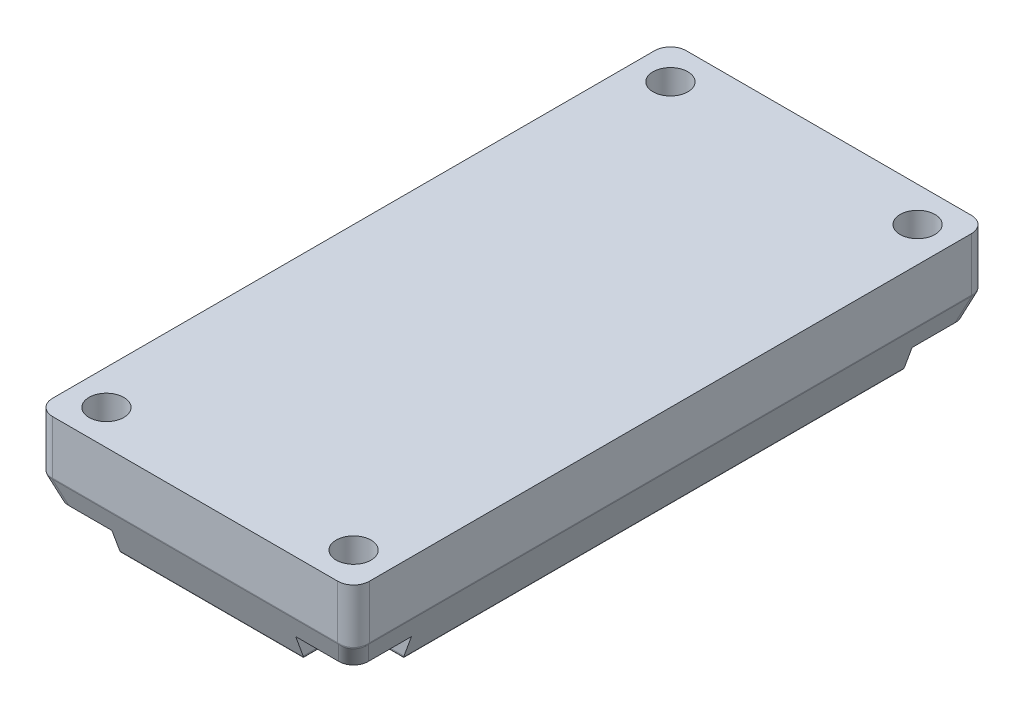
SolidWorks part; units mm, degrees
material "Polyethylene Cross-Linked"
ref_plane "Front Plane" through (0, 0, 0) normal (0, 0, 1) x (1, 0, 0)
ref_plane "Top Plane" through (0, 0, 0) normal (0, 1, 0) x (1, 0, 0)
ref_plane "Right Plane" through (0, 0, 0) normal (1, 0, 0) x (0, 0, -1)
sketch "Sketch1" plane through (0, 0, 0) normal (0, 1, 0) x (1, 0, 0)
  line L1 (-10, 20) -> (10, 20)
  line L2 (-10, 20) -> (-10, -20)
  line L3 (-10, -20) -> (10, -20)
  line L4 (10, 20) -> (10, -20)
  line L5 (-10, 20) -> (10, -20) construction
  line L6 (-10, -20) -> (10, 20) construction
  point P0 (0, 0)
  dimension "D1" = 20
  dimension "D2" = 40
extrude "Boss-Extrude1" add sketch "Sketch1" against normal blind 6.4
sketch "Sketch2" plane through (0, -6.4, 0) normal (0, -1, 0) x (-1, 0, 0)
  line L0 (5.8, -17.6) -> (5.8, -20)
  line L1 (10, -20) -> (-10, -20) construction
  line L2 (7.6, -15.8) -> (10, -15.8)
  line L3 (10, 20) -> (10, -20) construction
  line L4 (5.8, -20) -> (10, -20)
  line L5 (10, -20) -> (10, -15.8)
  arc A0 (7.6, -15.8) -> (5.8, -17.6) centre (7.6, -17.6) ccw
  dimension "D3" = 3.6
  dimension "D1" = 4.2
  dimension "D2" = 4.2
extrude "Cut-Extrude1" cut sketch "Sketch2" against normal blind 1.5
hole_wizard "M2 Clearance Hole1" positions "Sketch8" profile "Sketch7" hole size "M2" standard "ANSI Metric" end condition through all
sketch "Sketch8" plane through (0, -4.9, 0) normal (0, -1, 0) x (-1, 0, 0)
  line L0 (10, -20) -> (10, -15.8) construction
  line L1 (5.8, -20) -> (10, -20) construction
  point P0 (7.8, -17.8)
  dimension "D1" = 2.2
  dimension "D2" = 2.2
sketch "Sketch7" plane through (-7.8, -4.9, 17.8) normal (1, 0, 0) x (0, 0, -1)
  line L0 (0, 0) -> (0, 4.9)
  line L1 (0, 4.9) -> (1.1, 4.9)
  line L2 (1.1, 4.9) -> (1.1, 0)
  line L5 (1.1, 0) -> (0, 0)
  line L11 (0, -6.35) -> (0, 107.95) construction
  dimension "Thru Hole Dia." = 2.2
  dimension "Thru Hole Depth" = 4.9
mirror "Mirror1" about plane through (0, 0, 0) normal (1, 0, 0) of "M2 Clearance Hole1", "Cut-Extrude1"
mirror "Mirror2" about plane through (0, 0, 0) normal (0, 0, 1) of "Mirror1", "Cut-Extrude1"
sketch "Sketch3" plane through (0, 0, 0) normal (0, 0, 1) x (1, 0, 0)
  line L0 (10, -3.4) -> (10, -6.4)
  line L1 (10, -4.9) -> (10, 0) construction
  line L2 (10, -6.4) -> (8.9081, -6.4)
  line L3 (10, -6.4) -> (7.6, -6.4) construction
  line L4 (8.9081, -6.4) -> (10, -3.4)
  dimension "D1" = 3
  dimension "D2" = 20
extrude "Cut-Extrude2" cut sketch "Sketch3" against normal through all both and the other way through all
mirror "Mirror3" about plane through (0, 0, 0) normal (1, 0, 0) of "Cut-Extrude2"
sketch "Sketch4" plane through (0, 0, 0) normal (1, 0, 0) x (0, 0, -1)
  line L0 (20, -3.4) -> (18.9081, -6.4)
  line L1 (20, -3.4) -> (20, 0) construction
  line L2 (17.6, -6.4) -> (20, -6.4) construction
  line L3 (18.9081, -6.4) -> (20, -6.4)
  line L4 (20, -6.4) -> (20, -3.4)
  dimension "D1" = 3
  dimension "D2" = 20
extrude "Cut-Extrude3" cut sketch "Sketch4" against normal through all both and the other way through all
mirror "Mirror4" about plane through (0, 0, 0) normal (0, 0, 1) of "Cut-Extrude3"
fillet "Fillet1" radius 1 8 edges at (-9.727, -4.15, -19.727) (-10, -1.7, -20) (10, -1.7, -20) (9.727, -4.15, -19.727) (9.727, -4.15, 19.727) (10, -1.7, 20) (-10, -1.7, 20) (-9.727, -4.15, 19.727)
fillet "Fillet2" radius 0.2 32 edges at (-9.0293, -3.4012, 19.9996) (-9.7071, -3.4659, 19.7071) (-9.9996, -3.4012, 19.0293) (-10, -3.4, 0) (-9.9996, -3.4012, -19.0293) (-9.7071, -3.4659, -19.7071) (-9.0293, -3.4012, -19.9996) (0, -3.4, -20) (9.0293, -3.4012, -19.9996) (9.7071, -3.4659, -19.7071) (9.9996, -3.4012, -19.0293) (10, -3.4, 0) (9.9996, -3.4012, 19.0293) (9.7071, -3.4659, 19.7071) (9.0293, -3.4012, 19.9996) (5.8, -6.4, 18.254) (6.3272, -6.4, 16.3272) (8.254, -6.4, 15.8) (8.9081, -6.4, 0) (8.254, -6.4, -15.8) (6.3272, -6.4, -16.3272) (5.8, -6.4, -18.254) (0, -6.4, -18.9081) (-5.8, -6.4, -18.254) (-6.3272, -6.4, -16.3272) (-8.254, -6.4, -15.8) (-8.9081, -6.4, 0) (-8.254, -6.4, 15.8) (-6.3272, -6.4, 16.3272) (-5.8, -6.4, 18.254) (0, -6.4, 18.9081) (0, -3.4, 20)
